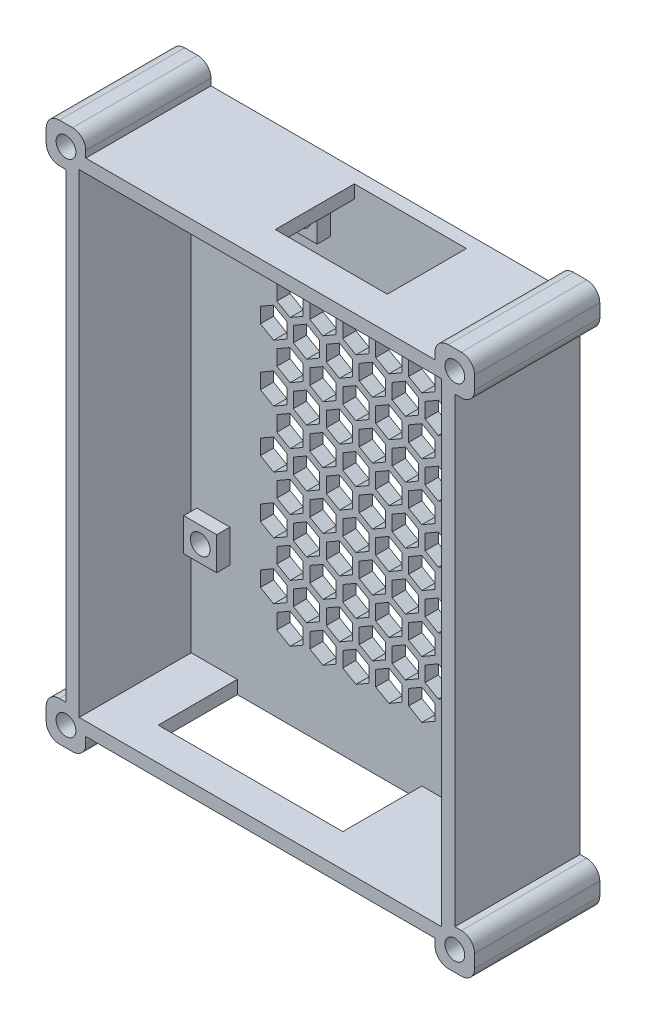
SolidWorks part; units mm, degrees
ref_plane "Front Plane" through (0, 0, 0) normal (0, 0, 1) x (1, 0, 0)
ref_plane "Top Plane" through (0, 0, 0) normal (0, 1, 0) x (1, 0, 0)
ref_plane "Right Plane" through (0, 0, 0) normal (1, 0, 0) x (0, 0, -1)
sketch "Sketch1" plane through (0, 0, 0) normal (0, 0, 1) x (1, 0, 0)
  line L1 (-27.5, -36) -> (27.5, -36)
  line L2 (-27.5, -36) -> (-27.5, 36)
  line L3 (-27.5, 36) -> (27.5, 36)
  line L4 (27.5, -36) -> (27.5, 36)
  line L5 (-27.5, -36) -> (27.5, 36) construction
  line L6 (-27.5, 36) -> (27.5, -36) construction
  point P0 (0, 0)
  dimension "D1" = 72
  dimension "D2" = 55
extrude "Boss-Extrude1" add sketch "Sketch1" along normal blind 2 from offset 1
sketch "Sketch2" plane through (0, 0, 3) normal (0, 0, 1) x (1, 0, 0)
  line L1 (-27.5, -36) -> (27.5, -36)
  line L2 (-27.5, -36) -> (-27.5, 36)
  line L3 (-27.5, 36) -> (27.5, 36)
  line L4 (27.5, -36) -> (27.5, 36)
  line L8 (-29.5, -38) -> (29.5, -38)
  line L9 (29.5, -38) -> (29.5, 38)
  line L10 (-29.5, 38) -> (29.5, 38)
  line L11 (-29.5, -38) -> (-29.5, 38)
  point P0 (0, 0)
  dimension "D1" = 2
extrude "Boss-Extrude2" add sketch "Sketch2" along normal blind 17 and the other way blind 2
sketch "Sketch5" plane through (0, 0, 3) normal (0, 0, 1) x (-1, 0, 0)
  line L1 (-24.13, 22.82) -> (-21.63, 22.82)
  line L2 (-21.63, 22.82) -> (-21.63, 17.82)
  line L3 (-21.63, 17.82) -> (-26.63, 17.82)
  line L5 (-26.63, 17.82) -> (-26.63, 22.82)
  line L6 (-26.63, 22.82) -> (-24.13, 22.82)
  line L7 (24.13, 21.55) -> (21.63, 21.55)
  line L8 (21.63, 21.55) -> (21.63, 16.55)
  line L9 (21.63, 16.55) -> (26.63, 16.55)
  line L10 (26.63, 16.55) -> (26.63, 21.55)
  line L11 (26.63, 21.55) -> (24.13, 21.55)
  line L12 (-19.05, -29.25) -> (-16.55, -29.25)
  line L13 (-16.55, -29.25) -> (-16.55, -34.25)
  line L14 (-16.55, -34.25) -> (-21.55, -34.25)
  line L15 (-21.55, -34.25) -> (-21.55, -29.25)
  line L16 (-21.55, -29.25) -> (-19.05, -29.25)
  line L17 (8.89, -29.25) -> (11.39, -29.25)
  line L18 (11.39, -29.25) -> (11.39, -34.25)
  line L19 (11.39, -34.25) -> (6.39, -34.25)
  line L20 (6.39, -34.25) -> (6.39, -29.25)
  line L21 (6.39, -29.25) -> (8.89, -29.25)
  circle A0 centre (-24.13, 20.32) radius 1.5
  circle A1 centre (24.13, 19.05) radius 1.5
  circle A2 centre (-19.05, -31.75) radius 1.5
  circle A3 centre (8.89, -31.75) radius 1.5
  point P0 (0, 0)
extrude "Boss-Extrude3" add sketch "Sketch5" along normal blind 2
sketch "Sketch6" plane through (0, 0, 3) normal (0, 0, 1) x (1, 0, 0)
  circle A0 centre (19.05, 31.75) radius 1.5
  circle A1 centre (-8.89, 31.75) radius 1.5
  circle A2 centre (-24.13, -19.05) radius 1.5
  circle A3 centre (24.13, -20.32) radius 1.5
extrude "Cut-Extrude3" cut sketch "Sketch6" against normal blind 2
sketch "Sketch8" plane through (0, 0, 3) normal (0, 0, 1) x (1, 0, 0)
  line L30 (-7.5, 20.2695) -> (-9.5, 19.1148)
  line L31 (-10, 24.5996) -> (-12, 23.4449)
  line L32 (-12, 23.4449) -> (-12, 21.1355)
  line L33 (-12, 21.1355) -> (-10, 19.9808)
  line L34 (-10, 19.9808) -> (-8, 21.1355)
  line L35 (-8, 21.1355) -> (-8, 23.4449)
  line L36 (-8, 23.4449) -> (-10, 24.5996)
  line L37 (-9.5, 19.1148) -> (-9.5, 16.8054)
  line L38 (-9.5, 16.8054) -> (-7.5, 15.6507)
  line L39 (-7.5, 15.6507) -> (-5.5, 16.8054)
  line L40 (-5.5, 16.8054) -> (-5.5, 19.1148)
  line L41 (-5.5, 19.1148) -> (-7.5, 20.2695)
  line L42 (-2.5, 20.2695) -> (-4.5, 19.1148)
  line L43 (-5, 24.5996) -> (-7, 23.4449)
  line L44 (-7, 23.4449) -> (-7, 21.1355)
  line L45 (-7, 21.1355) -> (-5, 19.9808)
  line L46 (-5, 19.9808) -> (-3, 21.1355)
  line L47 (-3, 21.1355) -> (-3, 23.4449)
  line L48 (-3, 23.4449) -> (-5, 24.5996)
  line L49 (-4.5, 19.1148) -> (-4.5, 16.8054)
  line L50 (-4.5, 16.8054) -> (-2.5, 15.6507)
  line L51 (-2.5, 15.6507) -> (-0.5, 16.8054)
  line L52 (-0.5, 16.8054) -> (-0.5, 19.1148)
  line L53 (-0.5, 19.1148) -> (-2.5, 20.2695)
  line L54 (2.5, 20.2695) -> (0.5, 19.1148)
  line L55 (0, 24.5996) -> (-2, 23.4449)
  line L56 (-2, 23.4449) -> (-2, 21.1355)
  line L57 (-2, 21.1355) -> (0, 19.9808)
  line L58 (0, 19.9808) -> (2, 21.1355)
  line L59 (2, 21.1355) -> (2, 23.4449)
  line L60 (2, 23.4449) -> (0, 24.5996)
  line L61 (0.5, 19.1148) -> (0.5, 16.8054)
  line L62 (0.5, 16.8054) -> (2.5, 15.6507)
  line L63 (2.5, 15.6507) -> (4.5, 16.8054)
  line L64 (4.5, 16.8054) -> (4.5, 19.1148)
  line L65 (4.5, 19.1148) -> (2.5, 20.2695)
  line L66 (7.5, 20.2695) -> (5.5, 19.1148)
  line L67 (5, 24.5996) -> (3, 23.4449)
  line L68 (3, 23.4449) -> (3, 21.1355)
  line L69 (3, 21.1355) -> (5, 19.9808)
  line L70 (5, 19.9808) -> (7, 21.1355)
  line L71 (7, 21.1355) -> (7, 23.4449)
  line L72 (7, 23.4449) -> (5, 24.5996)
  line L73 (5.5, 19.1148) -> (5.5, 16.8054)
  line L74 (5.5, 16.8054) -> (7.5, 15.6507)
  line L75 (7.5, 15.6507) -> (9.5, 16.8054)
  line L76 (9.5, 16.8054) -> (9.5, 19.1148)
  line L77 (9.5, 19.1148) -> (7.5, 20.2695)
  line L78 (12.5, 20.2695) -> (10.5, 19.1148)
  line L79 (10, 24.5996) -> (8, 23.4449)
  line L80 (8, 23.4449) -> (8, 21.1355)
  line L81 (8, 21.1355) -> (10, 19.9808)
  line L82 (10, 19.9808) -> (12, 21.1355)
  line L83 (12, 21.1355) -> (12, 23.4449)
  line L84 (12, 23.4449) -> (10, 24.5996)
  line L85 (10.5, 19.1148) -> (10.5, 16.8054)
  line L86 (10.5, 16.8054) -> (12.5, 15.6507)
  line L87 (12.5, 15.6507) -> (14.5, 16.8054)
  line L88 (14.5, 16.8054) -> (14.5, 19.1148)
  line L89 (14.5, 19.1148) -> (12.5, 20.2695)
  line L90 (-7.5, 11.6095) -> (-9.5, 10.4548)
  line L91 (-10, 15.9396) -> (-12, 14.7849)
  line L92 (-12, 14.7849) -> (-12, 12.4755)
  line L93 (-12, 12.4755) -> (-10, 11.3208)
  line L94 (-10, 11.3208) -> (-8, 12.4755)
  line L95 (-8, 12.4755) -> (-8, 14.7849)
  line L96 (-8, 14.7849) -> (-10, 15.9396)
  line L97 (-9.5, 10.4548) -> (-9.5, 8.1454)
  line L98 (-9.5, 8.1454) -> (-7.5, 6.9907)
  line L99 (-7.5, 6.9907) -> (-5.5, 8.1454)
  line L100 (-5.5, 8.1454) -> (-5.5, 10.4548)
  line L101 (-5.5, 10.4548) -> (-7.5, 11.6095)
  line L102 (-2.5, 11.6095) -> (-4.5, 10.4548)
  line L103 (-5, 15.9396) -> (-7, 14.7849)
  line L104 (-7, 14.7849) -> (-7, 12.4755)
  line L105 (-7, 12.4755) -> (-5, 11.3208)
  line L106 (-5, 11.3208) -> (-3, 12.4755)
  line L107 (-3, 12.4755) -> (-3, 14.7849)
  line L108 (-3, 14.7849) -> (-5, 15.9396)
  line L109 (-4.5, 10.4548) -> (-4.5, 8.1454)
  line L110 (-4.5, 8.1454) -> (-2.5, 6.9907)
  line L111 (-2.5, 6.9907) -> (-0.5, 8.1454)
  line L112 (-0.5, 8.1454) -> (-0.5, 10.4548)
  line L113 (-0.5, 10.4548) -> (-2.5, 11.6095)
  line L114 (2.5, 11.6095) -> (0.5, 10.4548)
  line L115 (0, 15.9396) -> (-2, 14.7849)
  line L116 (-2, 14.7849) -> (-2, 12.4755)
  line L117 (-2, 12.4755) -> (0, 11.3208)
  line L118 (0, 11.3208) -> (2, 12.4755)
  line L119 (2, 12.4755) -> (2, 14.7849)
  line L120 (2, 14.7849) -> (0, 15.9396)
  line L121 (0.5, 10.4548) -> (0.5, 8.1454)
  line L122 (0.5, 8.1454) -> (2.5, 6.9907)
  line L123 (2.5, 6.9907) -> (4.5, 8.1454)
  line L124 (4.5, 8.1454) -> (4.5, 10.4548)
  line L125 (4.5, 10.4548) -> (2.5, 11.6095)
  line L126 (7.5, 11.6095) -> (5.5, 10.4548)
  line L127 (5, 15.9396) -> (3, 14.7849)
  line L128 (3, 14.7849) -> (3, 12.4755)
  line L129 (3, 12.4755) -> (5, 11.3208)
  line L130 (5, 11.3208) -> (7, 12.4755)
  line L131 (7, 12.4755) -> (7, 14.7849)
  line L132 (7, 14.7849) -> (5, 15.9396)
  line L133 (5.5, 10.4548) -> (5.5, 8.1454)
  line L134 (5.5, 8.1454) -> (7.5, 6.9907)
  line L135 (7.5, 6.9907) -> (9.5, 8.1454)
  line L136 (9.5, 8.1454) -> (9.5, 10.4548)
  line L137 (9.5, 10.4548) -> (7.5, 11.6095)
  line L138 (12.5, 11.6095) -> (10.5, 10.4548)
  line L139 (10, 15.9396) -> (8, 14.7849)
  line L140 (8, 14.7849) -> (8, 12.4755)
  line L141 (8, 12.4755) -> (10, 11.3208)
  line L142 (10, 11.3208) -> (12, 12.4755)
  line L143 (12, 12.4755) -> (12, 14.7849)
  line L144 (12, 14.7849) -> (10, 15.9396)
  line L145 (10.5, 10.4548) -> (10.5, 8.1454)
  line L146 (10.5, 8.1454) -> (12.5, 6.9907)
  line L147 (12.5, 6.9907) -> (14.5, 8.1454)
  line L148 (14.5, 8.1454) -> (14.5, 10.4548)
  line L149 (14.5, 10.4548) -> (12.5, 11.6095)
  line L150 (-7.5, 2.9495) -> (-9.5, 1.7948)
  line L151 (-10, 7.2796) -> (-12, 6.1249)
  line L152 (-12, 6.1249) -> (-12, 3.8155)
  line L153 (-12, 3.8155) -> (-10, 2.6608)
  line L154 (-10, 2.6608) -> (-8, 3.8155)
  line L155 (-8, 3.8155) -> (-8, 6.1249)
  line L156 (-8, 6.1249) -> (-10, 7.2796)
  line L157 (-9.5, 1.7948) -> (-9.5, -0.5146)
  line L158 (-9.5, -0.5146) -> (-7.5, -1.6693)
  line L159 (-7.5, -1.6693) -> (-5.5, -0.5146)
  line L160 (-5.5, -0.5146) -> (-5.5, 1.7948)
  line L161 (-5.5, 1.7948) -> (-7.5, 2.9495)
  line L162 (-2.5, 2.9495) -> (-4.5, 1.7948)
  line L163 (-5, 7.2796) -> (-7, 6.1249)
  line L164 (-7, 6.1249) -> (-7, 3.8155)
  line L165 (-7, 3.8155) -> (-5, 2.6608)
  line L166 (-5, 2.6608) -> (-3, 3.8155)
  line L167 (-3, 3.8155) -> (-3, 6.1249)
  line L168 (-3, 6.1249) -> (-5, 7.2796)
  line L169 (-4.5, 1.7948) -> (-4.5, -0.5146)
  line L170 (-4.5, -0.5146) -> (-2.5, -1.6693)
  line L171 (-2.5, -1.6693) -> (-0.5, -0.5146)
  line L172 (-0.5, -0.5146) -> (-0.5, 1.7948)
  line L173 (-0.5, 1.7948) -> (-2.5, 2.9495)
  line L174 (2.5, 2.9495) -> (0.5, 1.7948)
  line L175 (0, 7.2796) -> (-2, 6.1249)
  line L176 (-2, 6.1249) -> (-2, 3.8155)
  line L177 (-2, 3.8155) -> (0, 2.6608)
  line L178 (0, 2.6608) -> (2, 3.8155)
  line L179 (2, 3.8155) -> (2, 6.1249)
  line L180 (2, 6.1249) -> (0, 7.2796)
  line L181 (0.5, 1.7948) -> (0.5, -0.5146)
  line L182 (0.5, -0.5146) -> (2.5, -1.6693)
  line L183 (2.5, -1.6693) -> (4.5, -0.5146)
  line L184 (4.5, -0.5146) -> (4.5, 1.7948)
  line L185 (4.5, 1.7948) -> (2.5, 2.9495)
  line L186 (7.5, 2.9495) -> (5.5, 1.7948)
  line L187 (5, 7.2796) -> (3, 6.1249)
  line L188 (3, 6.1249) -> (3, 3.8155)
  line L189 (3, 3.8155) -> (5, 2.6608)
  line L190 (5, 2.6608) -> (7, 3.8155)
  line L191 (7, 3.8155) -> (7, 6.1249)
  line L192 (7, 6.1249) -> (5, 7.2796)
  line L193 (5.5, 1.7948) -> (5.5, -0.5146)
  line L194 (5.5, -0.5146) -> (7.5, -1.6693)
  line L195 (7.5, -1.6693) -> (9.5, -0.5146)
  line L196 (9.5, -0.5146) -> (9.5, 1.7948)
  line L197 (9.5, 1.7948) -> (7.5, 2.9495)
  line L198 (12.5, 2.9495) -> (10.5, 1.7948)
  line L199 (10, 7.2796) -> (8, 6.1249)
  line L200 (8, 6.1249) -> (8, 3.8155)
  line L201 (8, 3.8155) -> (10, 2.6608)
  line L202 (10, 2.6608) -> (12, 3.8155)
  line L203 (12, 3.8155) -> (12, 6.1249)
  line L204 (12, 6.1249) -> (10, 7.2796)
  line L205 (10.5, 1.7948) -> (10.5, -0.5146)
  line L206 (10.5, -0.5146) -> (12.5, -1.6693)
  line L207 (12.5, -1.6693) -> (14.5, -0.5146)
  line L208 (14.5, -0.5146) -> (14.5, 1.7948)
  line L209 (14.5, 1.7948) -> (12.5, 2.9495)
  line L210 (-7.5, -5.7105) -> (-9.5, -6.8652)
  line L211 (-10, -1.3804) -> (-12, -2.5351)
  line L212 (-12, -2.5351) -> (-12, -4.8445)
  line L213 (-12, -4.8445) -> (-10, -5.9992)
  line L214 (-10, -5.9992) -> (-8, -4.8445)
  line L215 (-8, -4.8445) -> (-8, -2.5351)
  line L216 (-8, -2.5351) -> (-10, -1.3804)
  line L217 (-9.5, -6.8652) -> (-9.5, -9.1746)
  line L218 (-9.5, -9.1746) -> (-7.5, -10.3293)
  line L219 (-7.5, -10.3293) -> (-5.5, -9.1746)
  line L220 (-5.5, -9.1746) -> (-5.5, -6.8652)
  line L221 (-5.5, -6.8652) -> (-7.5, -5.7105)
  line L222 (-2.5, -5.7105) -> (-4.5, -6.8652)
  line L223 (-5, -1.3804) -> (-7, -2.5351)
  line L224 (-7, -2.5351) -> (-7, -4.8445)
  line L225 (-7, -4.8445) -> (-5, -5.9992)
  line L226 (-5, -5.9992) -> (-3, -4.8445)
  line L227 (-3, -4.8445) -> (-3, -2.5351)
  line L228 (-3, -2.5351) -> (-5, -1.3804)
  line L229 (-4.5, -6.8652) -> (-4.5, -9.1746)
  line L230 (-4.5, -9.1746) -> (-2.5, -10.3293)
  line L231 (-2.5, -10.3293) -> (-0.5, -9.1746)
  line L232 (-0.5, -9.1746) -> (-0.5, -6.8652)
  line L233 (-0.5, -6.8652) -> (-2.5, -5.7105)
  line L234 (2.5, -5.7105) -> (0.5, -6.8652)
  line L235 (0, -1.3804) -> (-2, -2.5351)
  line L236 (-2, -2.5351) -> (-2, -4.8445)
  line L237 (-2, -4.8445) -> (0, -5.9992)
  line L238 (0, -5.9992) -> (2, -4.8445)
  line L239 (2, -4.8445) -> (2, -2.5351)
  line L240 (2, -2.5351) -> (0, -1.3804)
  line L241 (0.5, -6.8652) -> (0.5, -9.1746)
  line L242 (0.5, -9.1746) -> (2.5, -10.3293)
  line L243 (2.5, -10.3293) -> (4.5, -9.1746)
  line L244 (4.5, -9.1746) -> (4.5, -6.8652)
  line L245 (4.5, -6.8652) -> (2.5, -5.7105)
  line L246 (7.5, -5.7105) -> (5.5, -6.8652)
  line L247 (5, -1.3804) -> (3, -2.5351)
  line L248 (3, -2.5351) -> (3, -4.8445)
  line L249 (3, -4.8445) -> (5, -5.9992)
  line L250 (5, -5.9992) -> (7, -4.8445)
  line L251 (7, -4.8445) -> (7, -2.5351)
  line L252 (7, -2.5351) -> (5, -1.3804)
  line L253 (5.5, -6.8652) -> (5.5, -9.1746)
  line L254 (5.5, -9.1746) -> (7.5, -10.3293)
  line L255 (7.5, -10.3293) -> (9.5, -9.1746)
  line L256 (9.5, -9.1746) -> (9.5, -6.8652)
  line L257 (9.5, -6.8652) -> (7.5, -5.7105)
  line L258 (12.5, -5.7105) -> (10.5, -6.8652)
  line L259 (10, -1.3804) -> (8, -2.5351)
  line L260 (8, -2.5351) -> (8, -4.8445)
  line L261 (8, -4.8445) -> (10, -5.9992)
  line L262 (10, -5.9992) -> (12, -4.8445)
  line L263 (12, -4.8445) -> (12, -2.5351)
  line L264 (12, -2.5351) -> (10, -1.3804)
  line L265 (10.5, -6.8652) -> (10.5, -9.1746)
  line L266 (10.5, -9.1746) -> (12.5, -10.3293)
  line L267 (12.5, -10.3293) -> (14.5, -9.1746)
  line L268 (14.5, -9.1746) -> (14.5, -6.8652)
  line L269 (14.5, -6.8652) -> (12.5, -5.7105)
  line L270 (-7.5, -14.3705) -> (-9.5, -15.5252)
  line L271 (-10, -10.0404) -> (-12, -11.1951)
  line L272 (-12, -11.1951) -> (-12, -13.5045)
  line L273 (-12, -13.5045) -> (-10, -14.6592)
  line L274 (-10, -14.6592) -> (-8, -13.5045)
  line L275 (-8, -13.5045) -> (-8, -11.1951)
  line L276 (-8, -11.1951) -> (-10, -10.0404)
  line L277 (-9.5, -15.5252) -> (-9.5, -17.8346)
  line L278 (-9.5, -17.8346) -> (-7.5, -18.9893)
  line L279 (-7.5, -18.9893) -> (-5.5, -17.8346)
  line L280 (-5.5, -17.8346) -> (-5.5, -15.5252)
  line L281 (-5.5, -15.5252) -> (-7.5, -14.3705)
  line L282 (-2.5, -14.3705) -> (-4.5, -15.5252)
  line L283 (-5, -10.0404) -> (-7, -11.1951)
  line L284 (-7, -11.1951) -> (-7, -13.5045)
  line L285 (-7, -13.5045) -> (-5, -14.6592)
  line L286 (-5, -14.6592) -> (-3, -13.5045)
  line L287 (-3, -13.5045) -> (-3, -11.1951)
  line L288 (-3, -11.1951) -> (-5, -10.0404)
  line L289 (-4.5, -15.5252) -> (-4.5, -17.8346)
  line L290 (-4.5, -17.8346) -> (-2.5, -18.9893)
  line L291 (-2.5, -18.9893) -> (-0.5, -17.8346)
  line L292 (-0.5, -17.8346) -> (-0.5, -15.5252)
  line L293 (-0.5, -15.5252) -> (-2.5, -14.3705)
  line L294 (2.5, -14.3705) -> (0.5, -15.5252)
  line L295 (0, -10.0404) -> (-2, -11.1951)
  line L296 (-2, -11.1951) -> (-2, -13.5045)
  line L297 (-2, -13.5045) -> (0, -14.6592)
  line L298 (0, -14.6592) -> (2, -13.5045)
  line L299 (2, -13.5045) -> (2, -11.1951)
  line L300 (2, -11.1951) -> (0, -10.0404)
  line L301 (0.5, -15.5252) -> (0.5, -17.8346)
  line L302 (0.5, -17.8346) -> (2.5, -18.9893)
  line L303 (2.5, -18.9893) -> (4.5, -17.8346)
  line L304 (4.5, -17.8346) -> (4.5, -15.5252)
  line L305 (4.5, -15.5252) -> (2.5, -14.3705)
  line L306 (7.5, -14.3705) -> (5.5, -15.5252)
  line L307 (5, -10.0404) -> (3, -11.1951)
  line L308 (3, -11.1951) -> (3, -13.5045)
  line L309 (3, -13.5045) -> (5, -14.6592)
  line L310 (5, -14.6592) -> (7, -13.5045)
  line L311 (7, -13.5045) -> (7, -11.1951)
  line L312 (7, -11.1951) -> (5, -10.0404)
  line L313 (5.5, -15.5252) -> (5.5, -17.8346)
  line L314 (5.5, -17.8346) -> (7.5, -18.9893)
  line L315 (7.5, -18.9893) -> (9.5, -17.8346)
  line L316 (9.5, -17.8346) -> (9.5, -15.5252)
  line L317 (9.5, -15.5252) -> (7.5, -14.3705)
  line L318 (12.5, -14.3705) -> (10.5, -15.5252)
  line L319 (10, -10.0404) -> (8, -11.1951)
  line L320 (8, -11.1951) -> (8, -13.5045)
  line L321 (8, -13.5045) -> (10, -14.6592)
  line L322 (10, -14.6592) -> (12, -13.5045)
  line L323 (12, -13.5045) -> (12, -11.1951)
  line L324 (12, -11.1951) -> (10, -10.0404)
  line L325 (10.5, -15.5252) -> (10.5, -17.8346)
  line L326 (10.5, -17.8346) -> (12.5, -18.9893)
  line L327 (12.5, -18.9893) -> (14.5, -17.8346)
  line L328 (14.5, -17.8346) -> (14.5, -15.5252)
  line L329 (14.5, -15.5252) -> (12.5, -14.3705)
  line L330 (-7.5, -23.0305) -> (-9.5, -24.1852)
  line L331 (-10, -18.7004) -> (-12, -19.8551)
  line L332 (-12, -19.8551) -> (-12, -22.1645)
  line L333 (-12, -22.1645) -> (-10, -23.3192)
  line L334 (-10, -23.3192) -> (-8, -22.1645)
  line L335 (-8, -22.1645) -> (-8, -19.8551)
  line L336 (-8, -19.8551) -> (-10, -18.7004)
  line L337 (-9.5, -24.1852) -> (-9.5, -26.4946)
  line L338 (-9.5, -26.4946) -> (-7.5, -27.6493)
  line L339 (-7.5, -27.6493) -> (-5.5, -26.4946)
  line L340 (-5.5, -26.4946) -> (-5.5, -24.1852)
  line L341 (-5.5, -24.1852) -> (-7.5, -23.0305)
  line L342 (-2.5, -23.0305) -> (-4.5, -24.1852)
  line L343 (-5, -18.7004) -> (-7, -19.8551)
  line L344 (-7, -19.8551) -> (-7, -22.1645)
  line L345 (-7, -22.1645) -> (-5, -23.3192)
  line L346 (-5, -23.3192) -> (-3, -22.1645)
  line L347 (-3, -22.1645) -> (-3, -19.8551)
  line L348 (-3, -19.8551) -> (-5, -18.7004)
  line L349 (-4.5, -24.1852) -> (-4.5, -26.4946)
  line L350 (-4.5, -26.4946) -> (-2.5, -27.6493)
  line L351 (-2.5, -27.6493) -> (-0.5, -26.4946)
  line L352 (-0.5, -26.4946) -> (-0.5, -24.1852)
  line L353 (-0.5, -24.1852) -> (-2.5, -23.0305)
  line L354 (2.5, -23.0305) -> (0.5, -24.1852)
  line L355 (0, -18.7004) -> (-2, -19.8551)
  line L356 (-2, -19.8551) -> (-2, -22.1645)
  line L357 (-2, -22.1645) -> (0, -23.3192)
  line L358 (0, -23.3192) -> (2, -22.1645)
  line L359 (2, -22.1645) -> (2, -19.8551)
  line L360 (2, -19.8551) -> (0, -18.7004)
  line L361 (0.5, -24.1852) -> (0.5, -26.4946)
  line L362 (0.5, -26.4946) -> (2.5, -27.6493)
  line L363 (2.5, -27.6493) -> (4.5, -26.4946)
  line L364 (4.5, -26.4946) -> (4.5, -24.1852)
  line L365 (4.5, -24.1852) -> (2.5, -23.0305)
  line L366 (7.5, -23.0305) -> (5.5, -24.1852)
  line L367 (5, -18.7004) -> (3, -19.8551)
  line L368 (3, -19.8551) -> (3, -22.1645)
  line L369 (3, -22.1645) -> (5, -23.3192)
  line L370 (5, -23.3192) -> (7, -22.1645)
  line L371 (7, -22.1645) -> (7, -19.8551)
  line L372 (7, -19.8551) -> (5, -18.7004)
  line L373 (5.5, -24.1852) -> (5.5, -26.4946)
  line L374 (5.5, -26.4946) -> (7.5, -27.6493)
  line L375 (7.5, -27.6493) -> (9.5, -26.4946)
  line L376 (9.5, -26.4946) -> (9.5, -24.1852)
  line L377 (9.5, -24.1852) -> (7.5, -23.0305)
  line L378 (12.5, -23.0305) -> (10.5, -24.1852)
  line L379 (10, -18.7004) -> (8, -19.8551)
  line L380 (8, -19.8551) -> (8, -22.1645)
  line L381 (8, -22.1645) -> (10, -23.3192)
  line L382 (10, -23.3192) -> (12, -22.1645)
  line L383 (12, -22.1645) -> (12, -19.8551)
  line L384 (12, -19.8551) -> (10, -18.7004)
  line L385 (10.5, -24.1852) -> (10.5, -26.4946)
  line L386 (10.5, -26.4946) -> (12.5, -27.6493)
  line L387 (12.5, -27.6493) -> (14.5, -26.4946)
  line L388 (14.5, -26.4946) -> (14.5, -24.1852)
  line L389 (14.5, -24.1852) -> (12.5, -23.0305)
  line L390 (-12.5, 11.6095) -> (-14.5, 10.4548)
  line L391 (-15, 15.9396) -> (-17, 14.7849)
  line L392 (-17, 14.7849) -> (-17, 12.4755)
  line L393 (-17, 12.4755) -> (-15, 11.3208)
  line L394 (-15, 11.3208) -> (-13, 12.4755)
  line L395 (-13, 12.4755) -> (-13, 14.7849)
  line L396 (-13, 14.7849) -> (-15, 15.9396)
  line L397 (-14.5, 10.4548) -> (-14.5, 8.1454)
  line L398 (-14.5, 8.1454) -> (-12.5, 6.9907)
  line L399 (-12.5, 6.9907) -> (-10.5, 8.1454)
  line L400 (-10.5, 8.1454) -> (-10.5, 10.4548)
  line L401 (-10.5, 10.4548) -> (-12.5, 11.6095)
  line L402 (-12.5, 2.9495) -> (-14.5, 1.7948)
  line L403 (-15, 7.2796) -> (-17, 6.1249)
  line L404 (-17, 6.1249) -> (-17, 3.8155)
  line L405 (-17, 3.8155) -> (-15, 2.6608)
  line L406 (-15, 2.6608) -> (-13, 3.8155)
  line L407 (-13, 3.8155) -> (-13, 6.1249)
  line L408 (-13, 6.1249) -> (-15, 7.2796)
  line L409 (-14.5, 1.7948) -> (-14.5, -0.5146)
  line L410 (-14.5, -0.5146) -> (-12.5, -1.6693)
  line L411 (-12.5, -1.6693) -> (-10.5, -0.5146)
  line L412 (-10.5, -0.5146) -> (-10.5, 1.7948)
  line L413 (-10.5, 1.7948) -> (-12.5, 2.9495)
  line L414 (-12.5, -5.7105) -> (-14.5, -6.8652)
  line L415 (-15, -1.3804) -> (-17, -2.5351)
  line L416 (-17, -2.5351) -> (-17, -4.8445)
  line L417 (-17, -4.8445) -> (-15, -5.9992)
  line L418 (-15, -5.9992) -> (-13, -4.8445)
  line L419 (-13, -4.8445) -> (-13, -2.5351)
  line L420 (-13, -2.5351) -> (-15, -1.3804)
  line L421 (-14.5, -6.8652) -> (-14.5, -9.1746)
  line L422 (-14.5, -9.1746) -> (-12.5, -10.3293)
  line L423 (-12.5, -10.3293) -> (-10.5, -9.1746)
  line L424 (-10.5, -9.1746) -> (-10.5, -6.8652)
  line L425 (-10.5, -6.8652) -> (-12.5, -5.7105)
  line L426 (-12.5, -14.3705) -> (-14.5, -15.5252)
  line L427 (-15, -10.0404) -> (-17, -11.1951)
  line L428 (-17, -11.1951) -> (-17, -13.5045)
  line L429 (-17, -13.5045) -> (-15, -14.6592)
  line L430 (-15, -14.6592) -> (-13, -13.5045)
  line L431 (-13, -13.5045) -> (-13, -11.1951)
  line L432 (-13, -11.1951) -> (-15, -10.0404)
  line L433 (-14.5, -15.5252) -> (-14.5, -17.8346)
  line L434 (-14.5, -17.8346) -> (-12.5, -18.9893)
  line L435 (-12.5, -18.9893) -> (-10.5, -17.8346)
  line L436 (-10.5, -17.8346) -> (-10.5, -15.5252)
  line L437 (-10.5, -15.5252) -> (-12.5, -14.3705)
  line L438 (-12.5, -23.0305) -> (-14.5, -24.1852)
  line L439 (-15, -18.7004) -> (-17, -19.8551)
  line L440 (-17, -19.8551) -> (-17, -22.1645)
  line L441 (-17, -22.1645) -> (-15, -23.3192)
  line L442 (-15, -23.3192) -> (-13, -22.1645)
  line L443 (-13, -22.1645) -> (-13, -19.8551)
  line L444 (-13, -19.8551) -> (-15, -18.7004)
  line L445 (-14.5, -24.1852) -> (-14.5, -26.4946)
  line L446 (-14.5, -26.4946) -> (-12.5, -27.6493)
  line L447 (-12.5, -27.6493) -> (-10.5, -26.4946)
  line L448 (-10.5, -26.4946) -> (-10.5, -24.1852)
  line L449 (-10.5, -24.1852) -> (-12.5, -23.0305)
  line L450 (-15, 24.5996) -> (-17, 23.4449)
  line L451 (-17, 23.4449) -> (-17, 21.1355)
  line L452 (-17, 21.1355) -> (-15, 19.9808)
  line L453 (-15, 19.9808) -> (-13, 21.1355)
  line L454 (-13, 21.1355) -> (-13, 23.4449)
  line L455 (-13, 23.4449) -> (-15, 24.5996)
  line L456 (-12.5, 20.1791) -> (-14.5, 19.0244)
  line L457 (-14.5, 19.0244) -> (-14.5, 16.715)
  line L458 (-14.5, 16.715) -> (-12.5, 15.5603)
  line L459 (-12.5, 15.5603) -> (-10.5, 16.715)
  line L460 (-10.5, 16.715) -> (-10.5, 19.0244)
  line L461 (-10.5, 19.0244) -> (-12.5, 20.1791)
  circle A0 centre (-15, 22.2902) radius 2 construction
  circle A1 centre (-10, 22.2902) radius 2 construction
  circle A2 centre (-5, 22.2902) radius 2 construction
  circle A3 centre (0, 22.2902) radius 2 construction
  circle A4 centre (5, 22.2902) radius 2 construction
  circle A5 centre (10, 22.2902) radius 2 construction
  circle A6 centre (-10, 13.6302) radius 2 construction
  circle A7 centre (-5, 13.6302) radius 2 construction
  circle A8 centre (0, 13.6302) radius 2 construction
  circle A9 centre (5, 13.6302) radius 2 construction
  circle A10 centre (10, 13.6302) radius 2 construction
  circle A11 centre (-10, 4.9702) radius 2 construction
  circle A12 centre (-5, 4.9702) radius 2 construction
  circle A13 centre (0, 4.9702) radius 2 construction
  circle A14 centre (5, 4.9702) radius 2 construction
  circle A15 centre (10, 4.9702) radius 2 construction
  circle A16 centre (-10, -3.6898) radius 2 construction
  circle A17 centre (-5, -3.6898) radius 2 construction
  circle A18 centre (0, -3.6898) radius 2 construction
  circle A19 centre (5, -3.6898) radius 2 construction
  circle A20 centre (10, -3.6898) radius 2 construction
  circle A21 centre (-10, -12.3498) radius 2 construction
  circle A22 centre (-5, -12.3498) radius 2 construction
  circle A23 centre (0, -12.3498) radius 2 construction
  circle A24 centre (5, -12.3498) radius 2 construction
  circle A25 centre (10, -12.3498) radius 2 construction
  circle A26 centre (-10, -21.0098) radius 2 construction
  circle A27 centre (-5, -21.0098) radius 2 construction
  circle A28 centre (0, -21.0098) radius 2 construction
  circle A29 centre (5, -21.0098) radius 2 construction
  circle A30 centre (10, -21.0098) radius 2 construction
  circle A31 centre (-12.5, 17.8697) radius 2 construction
  circle A32 centre (-15, 4.9702) radius 2 construction
  circle A33 centre (-15, -3.6898) radius 2 construction
  circle A34 centre (-15, -12.3498) radius 2 construction
  circle A35 centre (-15, -21.0098) radius 2 construction
extrude "Cut-Extrude4" cut sketch "Sketch8" against normal up to surface (2 mm away) up to face at (25.63, -20.32, 1)
sketch "Sketch11" plane through (0, 0, 20) normal (0, 0, 1) x (1, 0, 0)
  line L0 (-29.5, 38) -> (-29.5, 35)
  line L1 (-29.5, 38) -> (-29.5, -38) construction
  line L2 (-29.5, 35) -> (-32.5, 35)
  line L3 (-32.5, 35) -> (-32.5, 41)
  line L7 (-26.5, 41) -> (-26.5, 38)
  line L8 (29.5, 38) -> (-29.5, 38) construction
  line L9 (-26.5, 38) -> (-29.5, 38)
  line L10 (-32.5, 41) -> (-26.5, 41)
  line L13 (32.5, 41) -> (26.5, 41)
  line L14 (26.5, 38) -> (29.5, 38)
  line L15 (26.5, 41) -> (26.5, 38)
  line L16 (32.5, 35) -> (32.5, 41)
  line L17 (29.5, 35) -> (32.5, 35)
  line L18 (29.5, 38) -> (29.5, 35)
  line L19 (29.5, -38) -> (29.5, -35)
  line L20 (29.5, -35) -> (32.5, -35)
  line L21 (32.5, -35) -> (32.5, -41)
  line L22 (26.5, -41) -> (26.5, -38)
  line L23 (26.5, -38) -> (29.5, -38)
  line L24 (32.5, -41) -> (26.5, -41)
  line L25 (-32.5, -41) -> (-26.5, -41)
  line L26 (-26.5, -38) -> (-29.5, -38)
  line L27 (-26.5, -41) -> (-26.5, -38)
  line L28 (-32.5, -35) -> (-32.5, -41)
  line L29 (-29.5, -35) -> (-32.5, -35)
  line L30 (-29.5, -38) -> (-29.5, -35)
extrude "Boss-Extrude4" add sketch "Sketch11" against normal up to surface (19 mm away) up to face at (-7.5, -16.6799, 1)
fillet "Fillet1" radius 2 12 edges at (26.5, -41, 10.5) (32.5, -41, 10.5) (32.5, -35, 10.5) (-26.5, -41, 10.5) (-32.5, -41, 10.5) (-32.5, -35, 10.5) (26.5, 41, 10.5) (32.5, 35, 10.5) (32.5, 41, 10.5) (-32.5, 35, 10.5) (-26.5, 41, 10.5) (-32.5, 41, 10.5)
sketch "Sketch12" plane through (0, 0, 20) normal (0, 0, 1) x (1, 0, 0)
  circle A0 centre (-29.5, 38) radius 1.5
  circle A1 centre (29.5, 38) radius 1.5
  circle A2 centre (29.5, -38) radius 1.5
  circle A3 centre (-29.5, -38) radius 1.5
extrude "Cut-Extrude5" cut sketch "Sketch12" against normal up to surface (19 mm away) up to face at (0, 0, 1)
sketch "Sketch13" plane through (0, -38, 0) normal (0, -1, 0) x (1, 0, 0)
  line L0 (-10.5, 3) -> (4.5, 3)
  line L1 (7.5, 15) -> (4.5, 15)
  line L2 (-15.5, 3) -> (-10.5, 3)
  line L3 (4.5, 3) -> (7.5, 3)
  line L4 (7.5, 3) -> (7.5, 15)
  line L5 (4.5, 15) -> (-20.5, 15)
  line L6 (-20.5, 15) -> (-20.5, 3)
  line L7 (-20.5, 3) -> (-15.5, 3)
extrude "Cut-Extrude6" cut sketch "Sketch13" against normal up to surface (2 mm away) up to face at (0, -36, 11.5)
sketch "Sketch14" plane through (0, 38, 0) normal (0, 1, 0) x (1, 0, 0)
  line L0 (2.2608, -15) -> (14.2608, -15)
  line L1 (2.2608, -3) -> (-2.7392, -3)
  line L2 (2.2608, -3) -> (14.2608, -3)
  line L3 (14.2608, -3) -> (14.2608, -15)
  line L4 (-2.7392, -3) -> (-2.7392, -15)
  line L5 (-2.7392, -15) -> (2.2608, -15)
extrude "Cut-Extrude7" cut sketch "Sketch14" against normal up to surface (2 mm away) up to face at (0, 36, 11.5)
